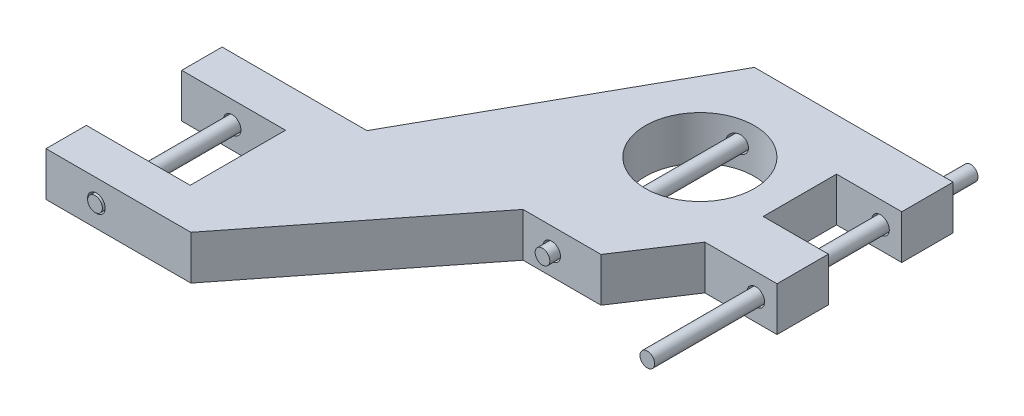
SolidWorks part; units mm, degrees
ref_plane "Front Plane" through (0, 0, 0) normal (0, 0, 1) x (1, 0, 0)
ref_plane "Top Plane" through (0, 0, 0) normal (0, 1, 0) x (1, 0, 0)
ref_plane "Right Plane" through (0, 0, 0) normal (1, 0, 0) x (0, 0, -1)
sketch "Sketch21" plane through (0, 0, 0) normal (0, 1, 0) x (1, 0, 0)
  line L0 (-25.2356, 32.747) -> (9.157, 32.747)
  line L1 (9.157, 32.747) -> (9.157, 23.857)
  line L2 (9.157, 23.857) -> (-2.1299, 23.857)
  line L3 (-2.1299, 23.857) -> (-2.1299, 11.157)
  line L4 (-2.1299, 11.157) -> (9.157, 11.157)
  line L5 (9.157, 11.157) -> (9.157, 2.267)
  line L6 (9.157, 2.267) -> (-3.3338, 2.267)
  line L7 (-3.3338, 2.267) -> (-10.476, -8.5709)
  line L8 (52.8639, 77.8829) -> (52.8639, -77.8829) construction
  line L10 (-49.2889, -10.2708) -> (-25.2356, 32.747)
  line L11 (-23.9745, -8.5709) -> (-10.476, -8.5709)
  line L12 (-49.2889, -40.7508) -> (-23.9745, -8.5709)
  line L20 (-74.3645, -33.7658) -> (-56.3967, -33.7658)
  line L21 (-56.3967, -33.7658) -> (-56.3967, -17.2558)
  line L22 (-56.3967, -17.2558) -> (-74.3645, -17.2558)
  line L23 (-74.3645, -40.7508) -> (-74.3645, -33.7658)
  line L24 (-74.3645, -10.2708) -> (-49.2889, -10.2708)
  line L25 (-49.2889, -10.2708) -> (-49.2889, -40.7508) construction
  line L26 (-74.3645, -40.7508) -> (-49.2889, -40.7508)
  line L27 (-74.3645, -17.2558) -> (-74.3645, -10.2708)
  circle A0 centre (-16.5131, 14.5845) radius 9.4369
  circle A1 centre (-16.0263, 13.6618) radius 17.0569 construction
  dimension "D1" = 12.7
  dimension "D2" = 16.51
  dimension "D4" = 30.48
  dimension "D5" = 30.48
  dimension "D6" = 8.89
extrude "Extrude1" add sketch "Sketch21" along normal mid plane 7.62 contours L26 L12 L11 L7 L6 L5 L4 L3 L2 L1 L0 L10 L24 L27 L22 L21 L20 L23 | A0
sketch "Sketch22" plane through (0, 0, 0) normal (0, 0, -1) x (-1, 0, 0)
  line L0 (74.3645, 0) -> (-19.991, 0) construction
  line L1 (74.3645, 3.81) -> (74.3645, -3.81) construction
  circle A0 centre (-5.4792, 0) radius 1.524
  circle A1 centre (65.6408, 0) radius 1.524
  circle A2 centre (19.0171, 0) radius 1.524
  dimension "D1" = 71.12
  dimension "D2" = 3.048
extrude "Cut-Extrude1" cut sketch "Sketch22" against normal mid plane 183.515
sketch "Sketch24" plane through (0, 0, 0) normal (0, 0, 1) x (1, 0, 0)
  circle A0 centre (-19.0171, 0) radius 1.27
  circle A1 centre (-65.6408, 0) radius 1.27
  circle A2 centre (5.4792, 0) radius 1.27
  dimension "D1" = 2.54
extrude "Extrude2" add sketch "Sketch24" against normal blind 40.005 from offset 10.16 separate body contours A0
extrude "Extrude3" add sketch "Sketch24<3>" against normal blind 55.974 from offset 16.51 separate body contours A2
sketch "Sketch24<3>" plane through (0, 0, 0) normal (0, 0, 1) x (1, 0, 0) same geometry as "Sketch24"
extrude "Extrude4" add sketch "Sketch24<4>" along normal blind 28.288 from offset 12.7 separate body contours A1
sketch "Sketch24<4>" plane through (0, 0, 0) normal (0, 0, 1) x (1, 0, 0) same geometry as "Sketch24"
